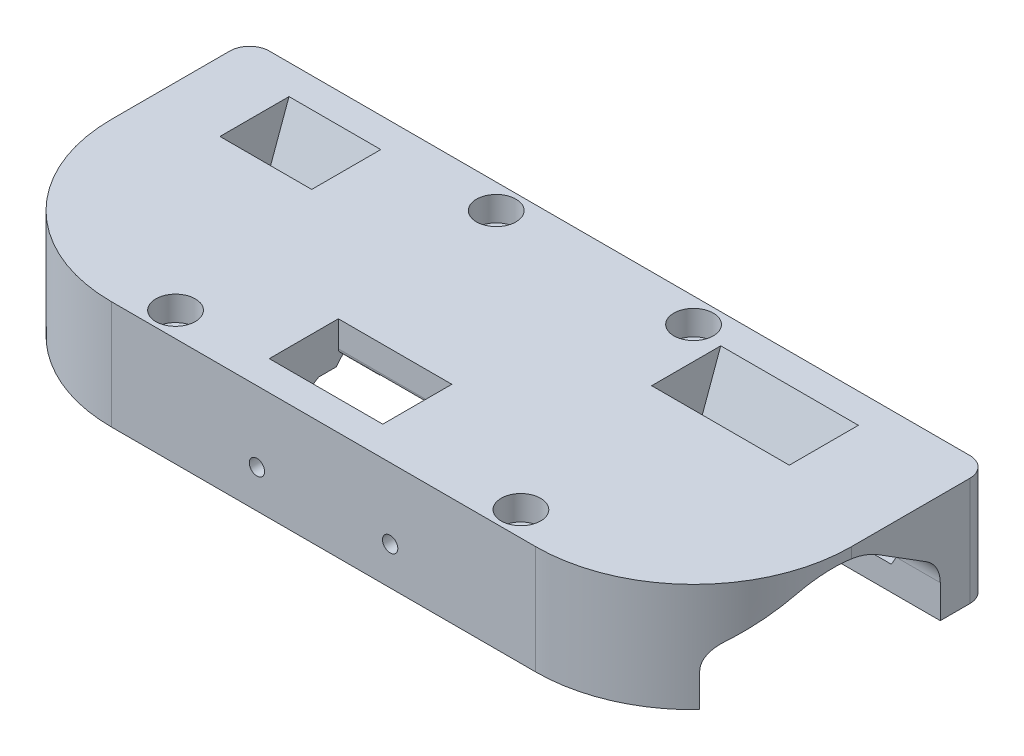
SolidWorks part; units mm, degrees
ref_plane "Front Plane" through (0, 0, 0) normal (0, 0, 1) x (1, 0, 0)
ref_plane "Top Plane" through (0, 0, 0) normal (0, 1, 0) x (1, 0, 0)
ref_plane "Right Plane" through (0, 0, 0) normal (1, 0, 0) x (0, 0, -1)
sketch "Sketch1" plane through (0, 0, 0) normal (1, 0, 0) x (0, 0, -1)
  line L0 (-30, -6) -> (-20, -6)
  line L1 (-20, -6) -> (-20, 14) construction
  line L2 (-20, 14) -> (20, 14) construction
  line L3 (20, 14) -> (20, -6) construction
  line L4 (20, -6) -> (30, -6)
  line L5 (30, -6) -> (30, 16)
  line L6 (30, 16) -> (-30, 16)
  line L7 (-30, 16) -> (-30, -6)
  line L8 (0, 0) -> (0, 16) construction
  line L9 (-7.4264, 11.868) -> (-17.1827, 5.7629)
  line L10 (7.4264, 11.868) -> (17.1827, 5.7629)
  line L11 (-20, 0.6766) -> (-20, -6)
  line L12 (20, -6) -> (20, 0.6766)
  circle A0 centre (0, 0) radius 14 construction
  arc A1 (7.4264, 11.868) -> (-7.4264, 11.868) centre (0, 0) ccw
  arc A2 (17.1827, 5.7629) -> (20, 0.6766) centre (14, 0.6766) cw
  arc A3 (-17.1827, 5.7629) -> (-20, 0.6766) centre (-14, 0.6766) ccw
  point P18 (20, 4)
  point P21 (-20, 4)
  dimension "D3" = 28
  dimension "D6" = 6
  dimension "D1" = 10
  dimension "D2" = 60
  dimension "D4" = 6
  dimension "D5" = 2
extrude "Boss-Extrude1" add sketch "Sketch1" along normal blind 75 and the other way blind 75
fillet "Fillet1" radius 32 2 edges at (-75, 5, 30) (75, 5, 30)
fillet "Fillet2" radius 4 2 edges at (-75, 5, -30) (75, 5, -30)
sketch "Sketch2" plane through (0, 0, -30) normal (0, 0, -1) x (-1, 0, 0)
  circle A0 centre (36.5, 1.7) radius 1.55
  circle A1 centre (63.5, 1.7) radius 1.55
  circle A2 centre (-36.5, 1.7) radius 1.55
  circle A3 centre (-63.5, 1.7) radius 1.55
  dimension "D1" = 3.1
extrude "Cut-Extrude1" cut sketch "Sketch2" against normal blind 30
sketch "Sketch3" plane through (0, 0, 30) normal (0, 0, 1) x (1, 0, 0)
  circle A0 centre (-13.5, 1.7) radius 1.55
  circle A1 centre (13.5, 1.7) radius 1.55
  dimension "D1" = 3.1
extrude "Cut-Extrude2" cut sketch "Sketch3" against normal blind 30
sketch "Sketch5" plane through (0, 0, 20) normal (0, 0, -1) x (-1, 0, 0)
  line L1 (-11.9123, 4.45) -> (-15.0877, 4.45)
  line L2 (-15.0877, 4.45) -> (-16.6754, 1.7)
  line L3 (-16.6754, 1.7) -> (-15.0877, -1.05)
  line L4 (-15.0877, -1.05) -> (-11.9123, -1.05)
  line L5 (-11.9123, -1.05) -> (-10.3246, 1.7)
  line L6 (-10.3246, 1.7) -> (-11.9123, 4.45)
  line L7 (11.9123, 4.45) -> (10.3246, 1.7)
  line L8 (10.3246, 1.7) -> (11.9123, -1.05)
  line L9 (11.9123, -1.05) -> (15.0877, -1.05)
  line L10 (15.0877, -1.05) -> (16.6754, 1.7)
  line L11 (16.6754, 1.7) -> (15.0877, 4.45)
  line L12 (15.0877, 4.45) -> (11.9123, 4.45)
  circle A0 centre (-13.5, 1.7) radius 2.75 construction
  circle A1 centre (13.5, 1.7) radius 2.75 construction
  dimension "D1" = 5.5
extrude "Cut-Extrude4" cut sketch "Sketch5" against normal blind 3.4 and the other way blind 25
sketch "Sketch6" plane through (0, -6, 0) normal (0, -1, 0) x (1, 0, 0)
  circle A0 centre (-20, -25) radius 2.1
  circle A2 centre (20, -25) radius 2.1
  circle A3 centre (35, 25) radius 2.1
  circle A4 centre (-35, 25) radius 2.1
  dimension "D1" = 4.2
extrude "Cut-Extrude5" cut sketch "Sketch6" against normal through all
hole_wizard "CBORE for M4 SHCS1" positions "Sketch8" profile "Sketch9" counterbore size "M4" standard "ANSI Metric" end condition through all
sketch "Sketch8" plane through (0, 16, 0) normal (0, 1, 0) x (1, 0, 0)
  point P0 (-20, 25)
  point P6 (20, 25)
  point P9 (35, -25)
  point P12 (-35, -25)
sketch "Sketch9" plane through (-20, 16, -25) normal (1, 0, 0) x (0, 0, 1)
  line L0 (0, 0) -> (0, 22)
  line L1 (0, 22) -> (2.25, 22)
  line L3 (2.25, 22) -> (2.25, 5)
  line L4 (2.25, 5) -> (4, 5)
  line L5 (4, 5) -> (4, 0)
  line L7 (4, 0) -> (0, 0)
  line L11 (0, -6.35) -> (0, 107.95) construction
  dimension "Thru Hole Dia." = 4.5
  dimension "Thru Hole Depth" = 22
  dimension "C'Bore Dia." = 8
  dimension "C'Bore Depth" = 5
ref_plane "Plane1" through (22.5, 0, 0) normal (1, 0, 0) x (0, 0, -1)
ref_plane "Plane2" through (-65, 0, 0) normal (-1, 0, 0) x (0, 0, 1)
ref_plane "Plane3" through (-21, 0, 0) normal (-1, 0, 0) x (0, 0, 1)
sketch "Sketch12" plane through (-65, 0, 0) normal (-1, 0, 0) x (0, 0, 1)
  line L0 (20, -6) -> (13, -6)
  line L1 (20, -6) -> (20, 0.6766)
  line L3 (-13.9866, 7.7629) -> (-7.4264, 11.868)
  line L4 (7.4264, 11.868) -> (17.1827, 5.7629)
  line L5 (13, 0) -> (13, -6)
  line L6 (-13.9866, 7.7629) -> (-10.4277, 7.7629)
  arc A0 (7.4264, 11.868) -> (-7.4264, 11.868) centre (0, 0) ccw
  arc A1 (13, 0) -> (-10.4277, 7.7629) centre (0, 0) ccw
  arc A2 (20, 0.6766) -> (17.1827, 5.7629) centre (14, 0.6766) ccw
  arc A3 (20, 0.6766) -> (17.1827, 5.7629) centre (14, 0.6766) ccw construction
  point P24 (0, 0)
  point P25 (0, 0)
  point P26 (-10.2642, 7.9779)
  point P29 (-13.9866, 7.7629)
  dimension "D1" = 26
extrude "Boss-Extrude2" add sketch "Sketch12" against normal blind 12
sketch "Sketch4" plane through (0, 0, -20) normal (0, 0, 1) x (1, 0, 0)
  line L1 (-38.0877, 4.45) -> (-39.6754, 1.7)
  line L2 (-39.6754, 1.7) -> (-38.0877, -1.05)
  line L3 (-38.0877, -1.05) -> (-34.9123, -1.05)
  line L4 (-34.9123, -1.05) -> (-33.3246, 1.7)
  line L5 (-33.3246, 1.7) -> (-34.9123, 4.45)
  line L6 (-34.9123, 4.45) -> (-38.0877, 4.45)
  line L7 (-65.0877, 4.45) -> (-66.6754, 1.7)
  line L8 (-66.6754, 1.7) -> (-65.0877, -1.05)
  line L9 (-65.0877, -1.05) -> (-61.9123, -1.05)
  line L10 (-61.9123, -1.05) -> (-60.3246, 1.7)
  line L11 (-60.3246, 1.7) -> (-61.9123, 4.45)
  line L12 (-61.9123, 4.45) -> (-65.0877, 4.45)
  line L13 (34.9123, 4.45) -> (33.3246, 1.7)
  line L14 (33.3246, 1.7) -> (34.9123, -1.05)
  line L15 (34.9123, -1.05) -> (38.0877, -1.05)
  line L16 (38.0877, -1.05) -> (39.6754, 1.7)
  line L17 (39.6754, 1.7) -> (38.0877, 4.45)
  line L18 (38.0877, 4.45) -> (34.9123, 4.45)
  line L19 (61.9123, 4.45) -> (60.3246, 1.7)
  line L20 (60.3246, 1.7) -> (61.9123, -1.05)
  line L21 (61.9123, -1.05) -> (65.0877, -1.05)
  line L22 (65.0877, -1.05) -> (66.6754, 1.7)
  line L23 (66.6754, 1.7) -> (65.0877, 4.45)
  line L24 (65.0877, 4.45) -> (61.9123, 4.45)
  circle A0 centre (-36.5, 1.7) radius 2.75 construction
  circle A1 centre (-63.5, 1.7) radius 2.75 construction
  circle A2 centre (36.5, 1.7) radius 2.75 construction
  circle A3 centre (63.5, 1.7) radius 2.75 construction
  dimension "D1" = 5.5
extrude "Cut-Extrude3" cut sketch "Sketch4" against normal blind 3.4 and the other way blind 25
extrude "Boss-Extrude3" add sketch "Sketch12<2>" against normal blind 12 from surface starting at plane "Plane1"
sketch "Sketch12<2>" plane through (-65, 0, 0) normal (-1, 0, 0) x (0, 0, 1) same geometry as "Sketch12"
sketch "Sketch13" plane through (-21, 0, 0) normal (-1, 0, 0) x (0, 0, 1)
  line L0 (-20, -6) -> (-13, -6)
  line L1 (-13, -6) -> (-13, 0)
  line L2 (-20, -6) -> (-20, 0.6766)
  line L3 (-17.1827, 5.7629) -> (-7.4264, 11.868)
  line L5 (13.9866, 7.7629) -> (7.4264, 11.868)
  line L6 (10.4277, 7.7629) -> (13.9866, 7.7629)
  arc A0 (10.4277, 7.7629) -> (-13, 0) centre (0, 0) ccw
  arc A2 (-17.1827, 5.7629) -> (-20, 0.6766) centre (-14, 0.6766) ccw
  arc A5 (7.4264, 11.868) -> (-7.4264, 11.868) centre (0, 0) ccw
  dimension "D1" = 26
extrude "Boss-Extrude4" add sketch "Sketch13" against normal blind 12
sketch "Sketch14" plane through (0, 16, 0) normal (0, 1, 0) x (1, 0, 0)
  line L0 (-60.9154, 20) -> (-39.0846, 20) construction
  line L1 (-42.4, 10) -> (-54.4, 10)
  line L2 (-42.4, 10) -> (-42.4, 20)
  line L3 (-42.4, 20) -> (-54.4, 20)
  line L4 (-54.4, 10) -> (-54.4, 20)
  line L5 (-42.4, 10) -> (-54.4, 20) construction
  line L6 (-42.4, 20) -> (-54.4, 10) construction
  line L7 (-9, 20) -> (33.9154, 20) construction
  line L8 (54.4, 10) -> (42.4, 10)
  line L9 (54.4, 10) -> (54.4, 20)
  line L10 (54.4, 20) -> (42.4, 20)
  line L11 (42.4, 10) -> (42.4, 20)
  line L12 (54.4, 10) -> (42.4, 20) construction
  line L13 (54.4, 20) -> (42.4, 10) construction
  line L14 (-9.7337, -20) -> (9.7337, -20) construction
  line L15 (6, -10) -> (-6, -10)
  line L16 (6, -10) -> (6, -20)
  line L17 (6, -20) -> (-6, -20)
  line L18 (-6, -10) -> (-6, -20)
  line L19 (6, -10) -> (-6, -20) construction
  line L20 (6, -20) -> (-6, -10) construction
  point P0 (-48.4, 15)
  point P7 (48.4, 15)
  point P14 (0, -15)
  dimension "D1" = 48.4
  dimension "D2" = 48.4
  dimension "D3" = 10
  dimension "D4" = 12
extrude "Cut-Extrude8" cut sketch "Sketch14" against normal through all
sketch "Sketch15" plane through (0, 16, 0) normal (0, 1, 0) x (1, 0, 0)
  line L1 (-54.4, 20) -> (-61, 20)
  line L2 (-54.4, 20) -> (-54.4, 10)
  line L3 (-54.4, 10) -> (-61, 10)
  line L4 (-61, 20) -> (-61, 10)
  line L6 (-6, -20) -> (-17, -20)
  line L7 (-6, -20) -> (-6, -10)
  line L8 (-6, -10) -> (-17, -10)
  line L9 (-17, -20) -> (-17, -10)
  line L11 (42.4, 20) -> (26.5, 20)
  line L12 (42.4, 20) -> (42.4, 10)
  line L13 (42.4, 10) -> (26.5, 10)
  line L14 (26.5, 20) -> (26.5, 10)
  line L15 (42.4, 10) -> (54.4, 10) construction
  line L16 (6, -10) -> (-6, -10) construction
  line L17 (-54.4, 10) -> (-42.4, 10) construction
  line L18 (-65, 12.1) -> (-65, -12.1) construction
  line L19 (-21, 12.1) -> (-21, -12.1) construction
  line L20 (22.5, -12.1) -> (22.5, 12.1) construction
  dimension "D1" = 4
  dimension "D2" = 4
  dimension "D3" = 4
extrude "Cut-Extrude9" cut sketch "Sketch15" against normal through all
fillet "Fillet3" radius 1 3 edges at (30.5, 8.3066, -10) (-13, 8.3066, 10) (-57, 8.3066, -10)
chamfer "Chamfer1" distance 4 angle 70 3 edges at (40.45, 16, -20) (-51.7, 16, -20) (-5.5, 16, 20) first distance on face at (40.45, 16, -15)
